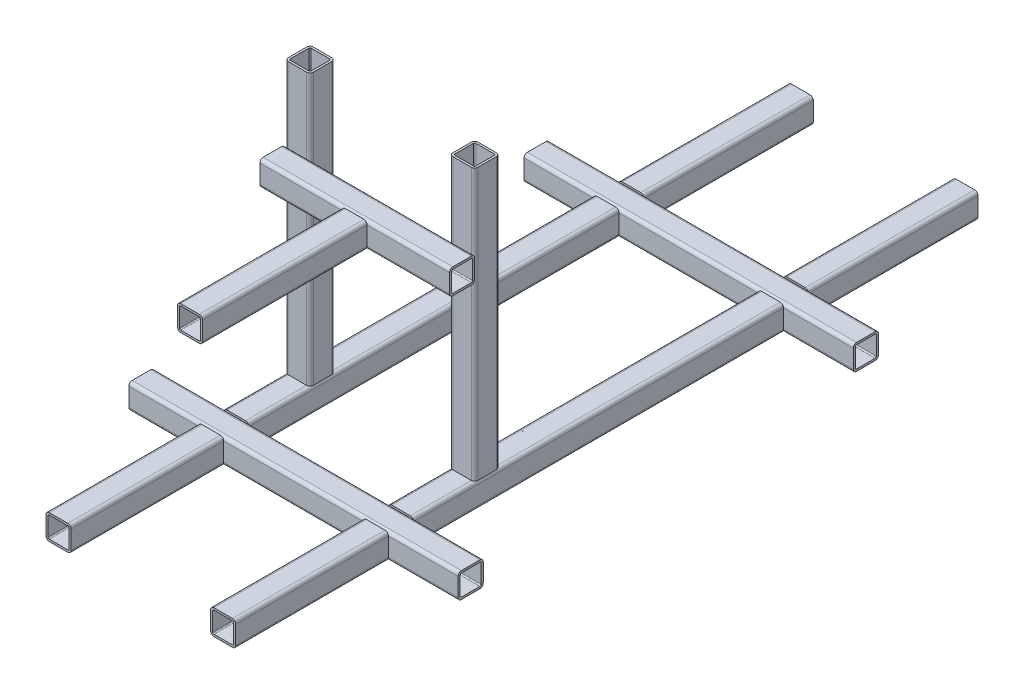
SolidWorks part; units mm, degrees
material "Alumina"
ref_plane "Front Plane" through (0, 0, 0) normal (0, 0, 1) x (1, 0, 0)
ref_plane "Top Plane" through (0, 0, 0) normal (0, 1, 0) x (1, 0, 0)
ref_plane "Right Plane" through (0, 0, 0) normal (1, 0, 0) x (0, 0, -1)
ref_plane "Bottom Face" through (0, 0, 0) normal (0, 1, 0) x (1, 0, 0)
ref_plane "Top Face" through (0, 38.1, 0) normal (0, 1, 0) x (1, 0, 0)
ref_plane "Mid Plane" through (0, 19.05, 0) normal (0, 1, 0) x (1, 0, 0)
ref_plane "Front Face" through (0, 0, 500) normal (0, 0, 1) x (1, 0, 0)
ref_plane "Back Face" through (0, 0, -500) normal (0, 0, 1) x (1, 0, 0)
ref_plane "Left Face" through (250, 0, 0) normal (1, 0, 0) x (0, 0, -1)
ref_plane "Right Face" through (-250, 0, 0) normal (1, 0, 0) x (0, 0, -1)
ref_plane "Divider Plane" through (0, 0, 150) normal (0, 0, 1) x (1, 0, 0)
ref_plane "Max Height Plane" through (0, 450, 0) normal (0, 1, 0) x (1, 0, 0)
ref_plane "Electronics Box Plane" through (0, 338.1, 0) normal (0, 1, 0) x (1, 0, 0)
sketch "Sketch2" plane through (250, 0, 0) normal (1, 0, 0) x (0, 0, -1)
  line L0 (330, 38.1) -> (-330, 38.1) construction
  line L5 (330, 0) -> (-330, 0) construction
  line L6 (0, 220) -> (0, -220) construction
  line L7 (-314.05, 38.1) -> (-285.95, 38.1)
  line L8 (-280.95, 33.1) -> (-280.95, 5)
  line L9 (-315.875, 33.1) -> (-315.875, 5)
  line L10 (-314.05, 3.175) -> (-285.95, 3.175)
  line L11 (-285.95, 0) -> (-314.05, 0)
  line L12 (-319.05, 5) -> (-319.05, 33.1)
  line L13 (-300, 38.1) -> (-300, 0) construction
  line L14 (-319.05, 19.05) -> (-280.95, 19.05) construction
  line L15 (-284.125, 5) -> (-284.125, 33.1)
  line L16 (-285.95, 34.925) -> (-314.05, 34.925)
  line L17 (-300, 34.925) -> (-300, 3.175) construction
  line L18 (-315.875, 19.05) -> (-284.125, 19.05) construction
  arc A0 (-285.95, 38.1) -> (-280.95, 33.1) centre (-285.95, 33.1) cw
  arc A1 (-280.95, 5) -> (-285.95, 0) centre (-285.95, 5) cw
  arc A2 (-314.05, 0) -> (-319.05, 5) centre (-314.05, 5) cw
  arc A3 (-319.05, 33.1) -> (-314.05, 38.1) centre (-314.05, 33.1) cw
  arc A4 (-315.875, 5) -> (-314.05, 3.175) centre (-314.05, 5) ccw
  arc A5 (-285.95, 3.175) -> (-284.125, 5) centre (-285.95, 5) ccw
  arc A6 (-284.125, 33.1) -> (-285.95, 34.925) centre (-285.95, 33.1) ccw
  arc A7 (-314.05, 34.925) -> (-315.875, 33.1) centre (-314.05, 33.1) ccw
  point P20 (-300, 19.05)
  point P39 (-300, 19.05)
  dimension "D1" = 5
  dimension "D2" = 300
  dimension "D3" = 3.175
extrude "Front Cross-Car Member" add sketch "Sketch2" against normal up to surface (500 mm away) up to plane "Right Face"
sketch "Sketch5" plane through (250, 0, 0) normal (1, 0, 0) x (0, 0, -1)
  line L0 (285.95, 38.1) -> (314.05, 38.1)
  line L1 (319.05, 33.1) -> (319.05, 5)
  line L2 (314.05, 0) -> (285.95, 0)
  line L3 (280.95, 5) -> (280.95, 33.1)
  line L4 (300, 38.1) -> (300, 0) construction
  line L5 (280.95, 19.05) -> (319.05, 19.05) construction
  line L6 (285.95, 34.925) -> (314.05, 34.925)
  line L7 (315.875, 33.1) -> (315.875, 5)
  line L8 (314.05, 3.175) -> (285.95, 3.175)
  line L9 (284.125, 5) -> (284.125, 33.1)
  line L10 (300, 34.925) -> (300, 3.175) construction
  line L11 (284.125, 19.05) -> (315.875, 19.05) construction
  line L12 (330, 0) -> (-330, 0) construction
  line L14 (330, 38.1) -> (-330, 38.1) construction
  line L15 (0, 220) -> (0, -220) construction
  arc A0 (314.05, 38.1) -> (319.05, 33.1) centre (314.05, 33.1) cw
  arc A1 (319.05, 5) -> (314.05, 0) centre (314.05, 5) cw
  arc A2 (285.95, 0) -> (280.95, 5) centre (285.95, 5) cw
  arc A3 (280.95, 33.1) -> (285.95, 38.1) centre (285.95, 33.1) cw
  arc A4 (314.05, 34.925) -> (315.875, 33.1) centre (314.05, 33.1) cw
  arc A5 (315.875, 5) -> (314.05, 3.175) centre (314.05, 5) cw
  arc A6 (285.95, 3.175) -> (284.125, 5) centre (285.95, 5) cw
  arc A7 (284.125, 33.1) -> (285.95, 34.925) centre (285.95, 33.1) cw
  point P32 (300, 19.05)
  point P33 (300, 19.05)
  dimension "D2" = 5
  dimension "D1" = 3.175
  dimension "D3" = 300
extrude "Back Cross-Car Member" add sketch "Sketch5" against normal up to surface (500 mm away) separate body up to plane "Right Face"
sketch "Sketch6" plane through (0, 0, -500) normal (0, 0, 1) x (1, 0, 0)
  line L0 (110.95, 38.1) -> (139.05, 38.1)
  line L1 (144.05, 33.1) -> (144.05, 5)
  line L2 (109.125, 33.1) -> (109.125, 5)
  line L3 (110.95, 3.175) -> (139.05, 3.175)
  line L4 (139.05, 0) -> (110.95, 0)
  line L5 (105.95, 5) -> (105.95, 33.1)
  line L6 (125, 38.1) -> (125, 0) construction
  line L7 (105.95, 19.05) -> (144.05, 19.05) construction
  line L8 (140.875, 5) -> (140.875, 33.1)
  line L9 (139.05, 34.925) -> (110.95, 34.925)
  line L10 (125, 34.925) -> (125, 3.175) construction
  line L11 (109.125, 19.05) -> (140.875, 19.05) construction
  line L12 (330, 38.1) -> (-330, 38.1) construction
  line L13 (330, 0) -> (-330, 0) construction
  line L14 (0, -220) -> (0, 220) construction
  arc A0 (139.05, 38.1) -> (144.05, 33.1) centre (139.05, 33.1) cw
  arc A1 (144.05, 5) -> (139.05, 0) centre (139.05, 5) cw
  arc A2 (110.95, 0) -> (105.95, 5) centre (110.95, 5) cw
  arc A3 (105.95, 33.1) -> (110.95, 38.1) centre (110.95, 33.1) cw
  arc A4 (109.125, 5) -> (110.95, 3.175) centre (110.95, 5) ccw
  arc A5 (139.05, 3.175) -> (140.875, 5) centre (139.05, 5) ccw
  arc A6 (140.875, 33.1) -> (139.05, 34.925) centre (139.05, 33.1) ccw
  arc A7 (110.95, 34.925) -> (109.125, 33.1) centre (110.95, 33.1) ccw
  point P16 (125, 19.05)
  point P33 (125, 19.05)
  dimension "D1" = 5
  dimension "D2" = 3.175
  dimension "D3" = 125
extrude "Back Left Along-Car Member" add sketch "Sketch6" along normal blind 180.95 and the other way blind 76.2
extrude "Middle Left Along-Car Member" add sketch "Sketch6<2>" along normal blind 561.9 from offset 219.05
sketch "Sketch6<2>" plane through (0, 0, -500) normal (0, 0, 1) x (1, 0, 0) same geometry as "Sketch6"
extrude "Front Left Along-Car Member" add sketch "Sketch6<3>" along normal blind 231.75 from offset 819.05
sketch "Sketch6<3>" plane through (0, 0, -500) normal (0, 0, 1) x (1, 0, 0) same geometry as "Sketch6"
sketch "Sketch7" plane through (0, 0, -500) normal (0, 0, 1) x (1, 0, 0)
  line L0 (-139.05, 38.1) -> (-110.95, 38.1)
  line L1 (-105.95, 33.1) -> (-105.95, 5)
  line L2 (-140.875, 33.1) -> (-140.875, 5)
  line L3 (-139.05, 3.175) -> (-110.95, 3.175)
  line L4 (-110.95, 0) -> (-139.05, 0)
  line L5 (-144.05, 5) -> (-144.05, 33.1)
  line L6 (-125, 38.1) -> (-125, 0) construction
  line L7 (-144.05, 19.05) -> (-105.95, 19.05) construction
  line L8 (-109.125, 5) -> (-109.125, 33.1)
  line L9 (-110.95, 34.925) -> (-139.05, 34.925)
  line L10 (-125, 34.925) -> (-125, 3.175) construction
  line L11 (-140.875, 19.05) -> (-109.125, 19.05) construction
  line L12 (330, 38.1) -> (-330, 38.1) construction
  line L13 (330, 0) -> (-330, 0) construction
  line L14 (0, -220) -> (0, 220) construction
  arc A0 (-110.95, 38.1) -> (-105.95, 33.1) centre (-110.95, 33.1) cw
  arc A1 (-105.95, 5) -> (-110.95, 0) centre (-110.95, 5) cw
  arc A2 (-139.05, 0) -> (-144.05, 5) centre (-139.05, 5) cw
  arc A3 (-144.05, 33.1) -> (-139.05, 38.1) centre (-139.05, 33.1) cw
  arc A4 (-140.875, 5) -> (-139.05, 3.175) centre (-139.05, 5) ccw
  arc A5 (-110.95, 3.175) -> (-109.125, 5) centre (-110.95, 5) ccw
  arc A6 (-109.125, 33.1) -> (-110.95, 34.925) centre (-110.95, 33.1) ccw
  arc A7 (-139.05, 34.925) -> (-140.875, 33.1) centre (-139.05, 33.1) ccw
  point P16 (-125, 19.05)
  point P33 (-125, 19.05)
  dimension "D1" = 5
  dimension "D2" = 3.175
  dimension "D3" = 125
extrude "Back Right Along-Car Member" add sketch "Sketch7" along normal blind 180.95 and the other way blind 76.2
extrude "Middle Right Along-Car Member" add sketch "Sketch7<2>" along normal blind 561.9 from offset 219.05
sketch "Sketch7<2>" plane through (0, 0, -500) normal (0, 0, 1) x (1, 0, 0) same geometry as "Sketch7"
extrude "Front Right Along-Car Member" add sketch "Sketch7<3>" along normal blind 231.75 from offset 819.05
sketch "Sketch7<3>" plane through (0, 0, -500) normal (0, 0, 1) x (1, 0, 0) same geometry as "Sketch7"
sketch "Sketch8" plane through (0, 38.1, 0) normal (0, 1, 0) x (1, 0, 0)
  line L0 (-139.05, -150) -> (-110.95, -150)
  line L1 (-105.95, -155) -> (-105.95, -183.1)
  line L2 (-140.875, -155) -> (-140.875, -183.1)
  line L3 (-139.05, -184.925) -> (-110.95, -184.925)
  line L4 (-110.95, -188.1) -> (-139.05, -188.1)
  line L5 (-144.05, -183.1) -> (-144.05, -155)
  line L6 (-125, -150) -> (-125, -188.1) construction
  line L7 (-144.05, -169.05) -> (-105.95, -169.05) construction
  line L8 (-109.125, -183.1) -> (-109.125, -155)
  line L9 (-110.95, -153.175) -> (-139.05, -153.175)
  line L10 (-125, -153.175) -> (-125, -184.925) construction
  line L11 (-140.875, -169.05) -> (-109.125, -169.05) construction
  line L12 (-220, -150) -> (220, -150) construction
  line L13 (0, -220) -> (0, 220) construction
  arc A0 (-110.95, -150) -> (-105.95, -155) centre (-110.95, -155) cw
  arc A1 (-105.95, -183.1) -> (-110.95, -188.1) centre (-110.95, -183.1) cw
  arc A2 (-139.05, -188.1) -> (-144.05, -183.1) centre (-139.05, -183.1) cw
  arc A3 (-144.05, -155) -> (-139.05, -150) centre (-139.05, -155) cw
  arc A4 (-140.875, -183.1) -> (-139.05, -184.925) centre (-139.05, -183.1) ccw
  arc A5 (-110.95, -184.925) -> (-109.125, -183.1) centre (-110.95, -183.1) ccw
  arc A6 (-109.125, -155) -> (-110.95, -153.175) centre (-110.95, -155) ccw
  arc A7 (-139.05, -153.175) -> (-140.875, -155) centre (-139.05, -155) ccw
  point P16 (-125, -169.05)
  point P33 (-125, -169.05)
  dimension "D1" = 5
  dimension "D2" = 3.175
  dimension "D3" = 38.1
  dimension "D4" = 125
extrude "Right Vertical Member" add sketch "Sketch8" along normal up to surface (411.9 mm away) up to plane "Max Height Plane"
sketch "Sketch10" plane through (0, 38.1, 0) normal (0, 1, 0) x (1, 0, 0)
  line L0 (110.95, -150) -> (139.05, -150)
  line L1 (144.05, -155) -> (144.05, -183.1)
  line L2 (109.125, -155) -> (109.125, -183.1)
  line L3 (110.95, -184.925) -> (139.05, -184.925)
  line L4 (139.05, -188.1) -> (110.95, -188.1)
  line L5 (105.95, -183.1) -> (105.95, -155)
  line L6 (125, -150) -> (125, -188.1) construction
  line L7 (105.95, -169.05) -> (144.05, -169.05) construction
  line L8 (140.875, -183.1) -> (140.875, -155)
  line L9 (139.05, -153.175) -> (110.95, -153.175)
  line L10 (125, -153.175) -> (125, -184.925) construction
  line L11 (109.125, -169.05) -> (140.875, -169.05) construction
  line L12 (-220, -150) -> (220, -150) construction
  line L13 (0, -220) -> (0, 220) construction
  arc A0 (139.05, -150) -> (144.05, -155) centre (139.05, -155) cw
  arc A1 (144.05, -183.1) -> (139.05, -188.1) centre (139.05, -183.1) cw
  arc A2 (110.95, -188.1) -> (105.95, -183.1) centre (110.95, -183.1) cw
  arc A3 (105.95, -155) -> (110.95, -150) centre (110.95, -155) cw
  arc A4 (109.125, -183.1) -> (110.95, -184.925) centre (110.95, -183.1) ccw
  arc A5 (139.05, -184.925) -> (140.875, -183.1) centre (139.05, -183.1) ccw
  arc A6 (140.875, -155) -> (139.05, -153.175) centre (139.05, -155) ccw
  arc A7 (110.95, -153.175) -> (109.125, -155) centre (110.95, -155) ccw
  point P16 (125, -169.05)
  point P33 (125, -169.05)
  dimension "D1" = 5
  dimension "D2" = 3.175
  dimension "D3" = 38.1
  dimension "D4" = 125
extrude "Left Vertical Member" add sketch "Sketch10" along normal up to surface (411.9 mm away) up to plane "Max Height Plane"
sketch "Sketch11" plane through (250, 0, 0) normal (1, 0, 0) x (0, 0, -1)
  line L0 (-221.2, 338.1) -> (-193.1, 338.1)
  line L1 (-188.1, 333.1) -> (-188.1, 305)
  line L2 (-223.025, 333.1) -> (-223.025, 305)
  line L3 (-221.2, 303.175) -> (-193.1, 303.175)
  line L4 (-193.1, 300) -> (-221.2, 300)
  line L5 (-226.2, 305) -> (-226.2, 333.1)
  line L6 (-207.15, 338.1) -> (-207.15, 300) construction
  line L7 (-226.2, 319.05) -> (-188.1, 319.05) construction
  line L8 (-191.275, 305) -> (-191.275, 333.1)
  line L9 (-193.1, 334.925) -> (-221.2, 334.925)
  line L10 (-207.15, 334.925) -> (-207.15, 303.175) construction
  line L11 (-223.025, 319.05) -> (-191.275, 319.05) construction
  line L12 (-150, 220) -> (-150, -220) construction
  line L13 (330, 338.1) -> (-330, 338.1) construction
  arc A0 (-193.1, 338.1) -> (-188.1, 333.1) centre (-193.1, 333.1) cw
  arc A1 (-188.1, 305) -> (-193.1, 300) centre (-193.1, 305) cw
  arc A2 (-221.2, 300) -> (-226.2, 305) centre (-221.2, 305) cw
  arc A3 (-226.2, 333.1) -> (-221.2, 338.1) centre (-221.2, 333.1) cw
  arc A4 (-223.025, 305) -> (-221.2, 303.175) centre (-221.2, 305) ccw
  arc A5 (-193.1, 303.175) -> (-191.275, 305) centre (-193.1, 305) ccw
  arc A6 (-191.275, 333.1) -> (-193.1, 334.925) centre (-193.1, 333.1) ccw
  arc A7 (-221.2, 334.925) -> (-223.025, 333.1) centre (-221.2, 333.1) ccw
  point P16 (-207.15, 319.05)
  point P33 (-207.15, 319.05)
  dimension "D1" = 5
  dimension "D2" = 3.175
  dimension "D3" = 38.1
  dimension "D4" = 38.1
extrude "Upper Cross-Car Member" add sketch "Sketch11" against normal blind 288.1 from offset 105.95 offset against normal yes
sketch "Sketch12" plane through (0, 0, 150) normal (0, 0, 1) x (1, 0, 0)
  line L0 (-14.05, 338.1) -> (14.05, 338.1)
  line L1 (19.05, 333.1) -> (19.05, 305)
  line L2 (-15.875, 333.1) -> (-15.875, 305)
  line L3 (-14.05, 303.175) -> (14.05, 303.175)
  line L4 (14.05, 300) -> (-14.05, 300)
  line L5 (-19.05, 305) -> (-19.05, 333.1)
  line L6 (0, 338.1) -> (0, 300) construction
  line L7 (-19.05, 319.05) -> (19.05, 319.05) construction
  line L8 (15.875, 305) -> (15.875, 333.1)
  line L9 (14.05, 334.925) -> (-14.05, 334.925)
  line L10 (0, 334.925) -> (0, 303.175) construction
  line L11 (-15.875, 319.05) -> (15.875, 319.05) construction
  line L12 (330, 338.1) -> (-330, 338.1) construction
  line L13 (0, -220) -> (0, 220) construction
  arc A0 (14.05, 338.1) -> (19.05, 333.1) centre (14.05, 333.1) cw
  arc A1 (19.05, 305) -> (14.05, 300) centre (14.05, 305) cw
  arc A2 (-14.05, 300) -> (-19.05, 305) centre (-14.05, 305) cw
  arc A3 (-19.05, 333.1) -> (-14.05, 338.1) centre (-14.05, 333.1) cw
  arc A4 (-15.875, 305) -> (-14.05, 303.175) centre (-14.05, 305) ccw
  arc A5 (14.05, 303.175) -> (15.875, 305) centre (14.05, 305) ccw
  arc A6 (15.875, 333.1) -> (14.05, 334.925) centre (14.05, 333.1) ccw
  arc A7 (-14.05, 334.925) -> (-15.875, 333.1) centre (-14.05, 333.1) ccw
  point P16 (0, 319.05)
  point P33 (0, 319.05)
  dimension "D1" = 5
  dimension "D2" = 3.175
  dimension "D3" = 38.1
extrude "E-Box Platform Base" add sketch "Sketch12" along normal blind 250 from offset 76.2
equation "\"D1@Front Face\" = \"frameLength@Master Assembly.SLDASM\" / 2"
equation "\"D1@Back Face\" = \"frameLength@Master Assembly.SLDASM\" / 2"
equation "\"D1@Left Face\"=\"frameWidth@Master Assembly.SLDASM\"/2"
equation "\"D1@Right Face\" = \"frameWidth@Master Assembly.SLDASM\" / 2"
equation "\"D1@Top Face\"=\"frameTubeStockHeight@Master Assembly.SLDASM\""
equation "\"D2@Sketch2\"=\"frameMemberDistLength@Master Assembly.SLDASM\"/2"
equation "\"D3@Sketch2\"=\"frameTubeStockWallThickness@Master Assembly.SLDASM\""
equation "\"D1@Sketch5\"=\"frameTubeStockWallThickness@Master Assembly.SLDASM\""
equation "\"D3@Sketch5\"=\"frameMemberDistLength@Master Assembly.SLDASM\"/2"
equation "\"D3@Sketch6\"=\"frameMemberDistWidth@Master Assembly.SLDASM\"/2"
equation "\"D1@Back Left Along-Car Member\"=( \"frameLength@Master Assembly.Assembly\" - \"frameMemberDistLength@Master Assembly.Assembly\" - \"frameTubeStockHeight@Master Assembly.Assembly\" )  / 2"
equation "\"D19@Middle Left Along-Car Member\" = ( \"frameLength@Master Assembly.SLDASM\" - \"frameMemberDistLength@Master Assembly.SLDASM\" + \"frameTubeStockHeight@Master Assembly.SLDASM\" ) / 2"
equation "\"D1@Middle Left Along-Car Member\"=\"frameMemberDistLength@Master Assembly.SLDASM\" - \"frameTubeStockHeight@Master Assembly.SLDASM\""
equation "\"D19@Front Left Along-Car Member\"=( \"frameLength@Master Assembly.SLDASM\" - \"frameMemberDistLength@Master Assembly.SLDASM\" )  / 2 + \"frameMemberDistLength@Master Assembly.SLDASM\" + \"frameTubeStockHeight@Master Assembly.SLDASM\" / 2"
equation "\"D1@Front Left Along-Car Member\" =  ( \"frameLength@Master Assembly.Assembly\" - \"frameMemberDistLength@Master Assembly.Assembly\" - \"frameTubeStockHeight@Master Assembly.Assembly\" )  / 2 + 2in"
equation "\"D3@Sketch7\"=\"frameMemberDistWidth@Master Assembly.SLDASM\"/2"
equation "\"D1@Back Right Along-Car Member\"=(\"frameLength@Master Assembly.SLDASM\" - \"frameMemberDistLength@Master Assembly.SLDASM\" - \"frameTubeStockHeight@Master Assembly.SLDASM\")  / 2"
equation "\"D19@Middle Right Along-Car Member\" = ( \"frameLength@Master Assembly.SLDASM\" - \"frameMemberDistLength@Master Assembly.SLDASM\" + \"frameTubeStockHeight@Master Assembly.SLDASM\" ) / 2"
equation "\"D1@Middle Right Along-Car Member\"=\"frameMemberDistLength@Master Assembly.SLDASM\" - \"frameTubeStockHeight@Master Assembly.SLDASM\""
equation "\"D19@Front Right Along-Car Member\"=( \"frameLength@Master Assembly.SLDASM\" - \"frameMemberDistLength@Master Assembly.SLDASM\" )  / 2 + \"frameMemberDistLength@Master Assembly.SLDASM\" + \"frameTubeStockHeight@Master Assembly.SLDASM\" / 2"
equation "\"D1@Front Right Along-Car Member\"=( \"frameLength@Master Assembly.Assembly\" - \"frameMemberDistLength@Master Assembly.Assembly\" - \"frameTubeStockHeight@Master Assembly.Assembly\" )  / 2 + 2in"
equation "\"D1@Divider Plane\"= \"frameDividerPlaneOffset@Master Assembly.SLDASM\""
equation "\"D3@Sketch8\"=\"frameTubeStockHeight@Master Assembly.SLDASM\""
equation "\"D4@Sketch8\"=\"frameMemberDistWidth@Master Assembly.SLDASM\"/2"
equation "\"D1@Max Height Plane\" = \"frameHeight@Master Assembly.SLDASM\""
equation "\"D4@Sketch10\"=\"frameMemberDistWidth@Master Assembly.SLDASM\"/2"
equation "\"D1@Electronics Box Plane\" = \"eboxPlaneHeight@Master Assembly.SLDASM\""
equation "\"D4@Sketch11\"=\"frameTubeStockHeight@Master Assembly.SLDASM\""
equation "\"D19@Upper Cross-Car Member\" = ( \"frameWidth@Master Assembly.SLDASM\" - \"frameMemberDistWidth@Master Assembly.SLDASM\" - \"frameTubeStockHeight@Master Assembly.SLDASM\" ) / 2"
equation "\"D1@Upper Cross-Car Member\" = \"frameMemberDistWidth@Master Assembly.SLDASM\" + \"frameTubeStockHeight@Master Assembly.SLDASM\""
equation "\"D19@E-Box Platform Base\"= \"frameTubeStockHeight@Master Assembly.SLDASM\" * 2"
equation "\"D2@Sketch6\"=\"frameTubeStockWallThickness@Master Assembly.SLDASM\""
equation "\"D2@Sketch7\"=\"frameTubeStockWallThickness@Master Assembly.SLDASM\""
equation "\"D2@Sketch8\"=\"frameTubeStockWallThickness@Master Assembly.SLDASM\""
equation "\"D3@Sketch10\"=\"frameTubeStockHeight@Master Assembly.SLDASM\""
equation "\"D2@Sketch10\"=\"frameTubeStockWallThickness@Master Assembly.SLDASM\""
equation "\"D3@Sketch11\"=\"frameTubeStockHeight@Master Assembly.SLDASM\""
equation "\"D2@Sketch11\"=\"frameTubeStockWallThickness@Master Assembly.SLDASM\""
equation "\"D3@Sketch12\"=\"frameTubeStockHeight@Master Assembly.SLDASM\""
equation "\"D2@Sketch12\"=\"frameTubeStockWallThickness@Master Assembly.SLDASM\""
